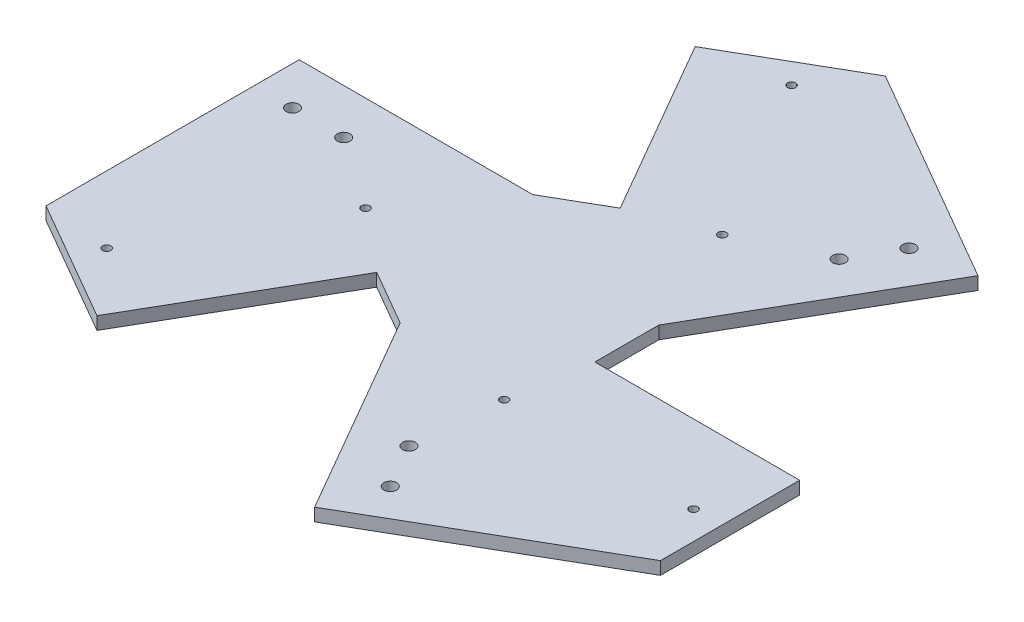
SolidWorks part; units mm, degrees
ref_plane "Front Plane" through (0, 0, 0) normal (0, 0, 1) x (1, 0, 0)
ref_plane "Top Plane" through (0, 0, 0) normal (0, 1, 0) x (1, 0, 0)
ref_plane "Right Plane" through (0, 0, 0) normal (1, 0, 0) x (0, 0, -1)
sketch "Sketch1" plane through (0, 0, 0) normal (0, 1, 0) x (1, 0, 0)
  line L0 (76.2, -43.9941) -> (76.2, 0) construction
  line L1 (76.2, -43.9941) -> (21.8271, -75.3863)
  line L2 (-18.2543, 18.7903) -> (-76.2, 18.7903)
  line L3 (-7.1457, -25.2038) -> (21.8271, -75.3863)
  line L4 (-76.2, -43.9941) -> (-76.2, 18.7903)
  line L5 (-76.2, -43.9941) -> (-38.1, -65.9911) construction
  line L6 (13.2547, -38.1978) -> (25013.2547, -43339.4679) construction
  line L7 (25.4, 6.4135) -> (25.4, -9.4615)
  line L8 (25.4, -9.4615) -> (76.2, -9.4615)
  line L9 (76.2, -9.4615) -> (76.2, -43.9941)
  line L10 (25.4, 6.4135) -> (54.3729, 56.596)
  line L11 (-46.2939, -61.2604) -> (-76.2, -43.9941)
  line L12 (-20.8939, -17.2663) -> (-46.2939, -61.2604)
  line L13 (0, 87.9882) -> (54.3729, 56.596)
  line L14 (-7.1457, -25.2038) -> (-20.8939, -17.2663)
  line L16 (0, 87.9882) -> (-38.1, 65.9911) construction
  line L17 (-29.9061, 70.7219) -> (0, 87.9882)
  line L18 (-4.5061, 26.7278) -> (-29.9061, 70.7219)
  line L20 (-18.2543, 18.7903) -> (-4.5061, 26.7278)
  line L21 (0, 0) -> (-49999.9986, 0) construction
  line L22 (0, 0) -> (-25000, 43301.2702) construction
  line L23 (0, 0) -> (-25000, -43301.2702) construction
  line L24 (25.4, 0) -> (76.2, 0) construction
  line L25 (-12.7, -21.997) -> (-38.1, -65.9911) construction
  line L26 (-12.7, 21.997) -> (-38.1, 65.9911) construction
  line L27 (76.2, 8.001) -> (76.2, 45.974) [skipped]
  line L28 (-31.1709, -69.9916) -> (1.7147, -88.9781) [skipped]
  line L29 (-45.0291, 61.9906) -> (-77.9147, 43.0041) [skipped]
  line L30 (-32.5457, -69.1979) -> (-7.1457, -25.2038) [skipped]
  line L31 (-43.6543, 62.7844) -> (-18.2543, 18.7903) [skipped]
  line L32 (76.2, 6.4135) -> (25.4, 6.4135) [skipped]
  circle A0 centre (69.2404, -28.829) radius 1.016
  circle A1 centre (0, 0) radius 76.2 construction
  circle A2 centre (-59.5868, -45.5494) radius 1.016
  circle A3 centre (-9.6536, 74.3784) radius 1.016
  circle A4 centre (22.2504, -28.829) radius 1.016
  circle A5 centre (-36.0918, -4.8549) radius 1.016
  circle A6 centre (13.8414, 33.6839) radius 1.016
  circle A7 centre (26.7384, -61.5522) radius 1.5875
  circle A8 centre (20.3884, -50.5537) radius 1.5875
  circle A9 centre (-53.975, 7.62) radius 1.5875
  circle A10 centre (-66.675, 7.62) radius 1.5875
  circle A11 centre (33.5866, 42.9337) radius 1.5875
  circle A12 centre (39.9366, 53.9322) radius 1.5875
  dimension "D2" = 15.875
  dimension "D6" = 152.4
  dimension "D13" = 2.032
  dimension "D17" = 2.032
  dimension "D21" = 3.175
  dimension "D22" = 3.175
  dimension "D1" = 120
  dimension "D3" = 50.8
  dimension "D4" = 3
  dimension "D5" = 3
  dimension "D7" = 9.4615
  dimension "D9" = 120
  dimension "D10" = 120
  dimension "D11" = 6.9596
  dimension "D12" = 19.3675
  dimension "D15" = 19.3675
  dimension "D16" = 53.9496
  dimension "D19" = 9.525
  dimension "D20" = 12.7
  dimension "D24" = 7.62
  dimension "D8" = 3
  dimension "D14" = 3
  dimension "D18" = 3
  dimension "D23" = 3
extrude "Boss-Extrude2" add sketch "Sketch1" along normal blind 3.175
